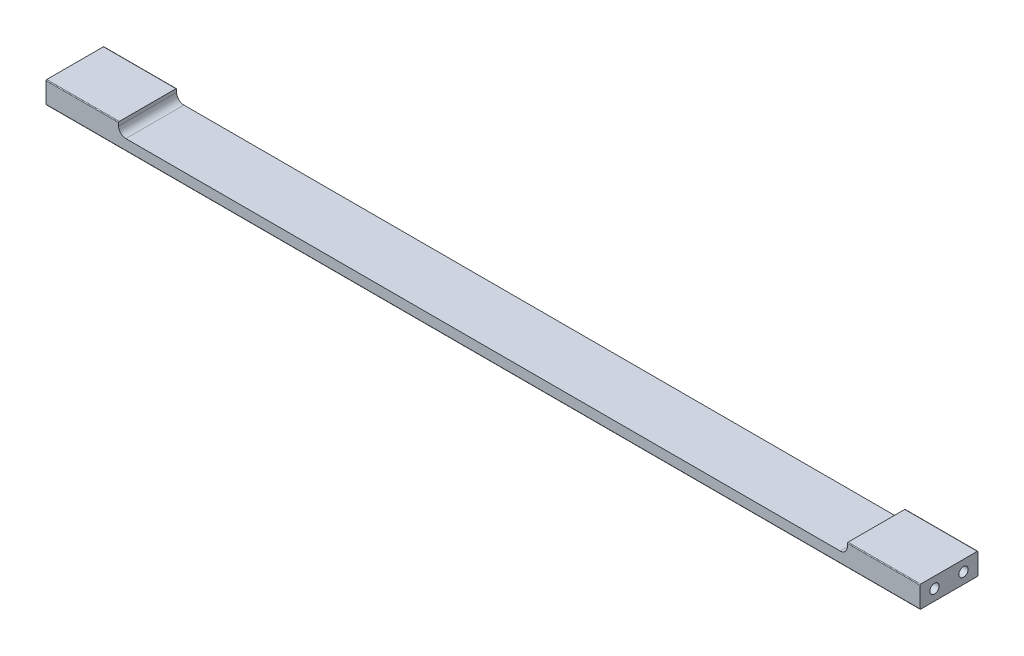
SolidWorks part; units mm, degrees
ref_plane "Front Plane" through (0, 0, 0) normal (0, 0, 1) x (1, 0, 0)
ref_plane "Top Plane" through (0, 0, 0) normal (0, 1, 0) x (1, 0, 0)
ref_plane "Right Plane" through (0, 0, 0) normal (1, 0, 0) x (0, 0, -1)
sketch "Sketch1" plane through (0, 0, 0) normal (0, 1, 0) x (1, 0, 0)
  line L1 (191.135, -12.7) -> (-191.135, -12.7)
  line L2 (191.135, -12.7) -> (191.135, 12.7)
  line L3 (191.135, 12.7) -> (-191.135, 12.7)
  line L4 (-191.135, -12.7) -> (-191.135, 12.7)
  line L5 (191.135, -12.7) -> (-191.135, 12.7) construction
  line L6 (191.135, 12.7) -> (-191.135, -12.7) construction
  point P0 (0, 0)
  dimension "Length" = 382.27
  dimension "Width" = 25.4
sketch "Sketch2" plane through (0, 0, 0) normal (1, 0, 0) x (0, 0, -1)
  line L0 (12.7, 4.7625) -> (12.7, -4.7625) construction
  point P2 (12.7, 0)
  dimension "Thickness" = 9.525
sketch "Sketch3" plane through (0, 0, 0) normal (0, 1, 0) x (1, 0, 0)
  line L1 (-191.135, 12.7) -> (191.135, 12.7)
  line L2 (-191.135, 12.7) -> (-191.135, -12.7)
  line L3 (-191.135, -12.7) -> (191.135, -12.7)
  line L4 (191.135, 12.7) -> (191.135, -12.7)
extrude "Boss-Extrude1" add sketch "Sketch3" against normal up to vertex (4.7625 mm away) and the other way up to vertex (4.7625 mm away) up to point (0, -4.7625, -12.7) other way up to point (0, 4.7625, -12.7)
fillet "Fillet1" radius 0.3143 4 edges at (0, -4.7625, 12.7) (0, -4.7625, -12.7) (0, 4.7625, -12.7) (0, 4.7625, 12.7)
sketch "Sketch4" plane through (-191.135, 0, 0) normal (-1, 0, 0) x (0, 0, 1)
  line L0 (0, 0) -> (6.35, 0) construction
  line L1 (0, 0) -> (-6.35, 0) construction
hole_wizard "Tap Drill for #10-32 Tap1" positions "Sketch5" profile "Sketch6" hole size "#10-32" standard "ANSI Inch"
sketch "Sketch5" plane through (-191.135, 0, 0) normal (-1, 0, 0) x (0, 0, 1)
  point P0 (-6.35, 0)
  point P3 (6.35, 0)
sketch "Sketch6" plane through (-191.135, 0, -6.35) normal (0, 1, 0) x (0, 0, 1)
  line L0 (0, 0) -> (0, 26.6133)
  line L1 (0, 26.6133) -> (2.0193, 25.4)
  line L2 (2.0193, 25.4) -> (2.0193, 0)
  line L5 (2.0193, 0) -> (0, 0)
  line L10 (0, 26.6133) -> (-2.0193, 25.4) construction
  line L11 (0, -6.35) -> (0, 107.95) construction
  dimension "Hole Dia." = 4.0386
  dimension "Hole Depth" = 25.4
  dimension "Drill Angle" = 118
hole_wizard "Tap Drill for #10-32 Tap2" positions "Sketch7" profile "Sketch8" hole size "#10-32" standard "ANSI Inch"
sketch "Sketch7" plane through (191.135, 0, 0) normal (1, 0, 0) x (0, 0, -1)
  point P0 (-6.35, 0)
  point P3 (6.35, 0)
sketch "Sketch8" plane through (191.135, 0, 6.35) normal (0, 1, 0) x (0, 0, -1)
  line L0 (0, 0) -> (0, 26.6133)
  line L1 (0, 26.6133) -> (2.0193, 25.4)
  line L2 (2.0193, 25.4) -> (2.0193, 0)
  line L5 (2.0193, 0) -> (0, 0)
  line L10 (0, 26.6133) -> (-2.0193, 25.4) construction
  line L11 (0, -6.35) -> (0, 107.95) construction
  dimension "Hole Dia." = 4.0386
  dimension "Hole Depth" = 25.4
  dimension "Drill Angle" = 118
sketch "Sketch9" plane through (0, 0, -12.7) normal (0, 0, -1) x (-1, 0, 0)
  line L0 (159.385, 4.7625) -> (159.385, 3.175)
  line L7 (-191.135, 4.7625) -> (191.135, 4.7625) construction
  line L8 (156.21, 0) -> (-156.21, 0)
  line L9 (-159.385, 3.175) -> (-159.385, 4.7625)
  line L10 (-159.385, 4.7625) -> (159.385, 4.7625)
  line L11 (191.135, 113.2574) -> (191.135, 38.2157) construction
  line L12 (-191.135, 113.2574) -> (-191.135, 38.2157) construction
  arc A0 (159.385, 3.175) -> (156.21, 0) centre (156.21, 3.175) cw
  arc A1 (-156.21, 0) -> (-159.385, 3.175) centre (-156.21, 3.175) cw
  point P15 (159.385, 0)
  point P18 (-159.385, 0)
  dimension "D4" = 3.175
  dimension "D1" = 31.75
  dimension "D2" = 31.75
  dimension "D3" = 4.7625
extrude "Cut-Extrude1" cut sketch "Sketch9" against normal through all
equation "\"D1@Fillet1\" = \"Thickness@Sketch2\" * .033"
